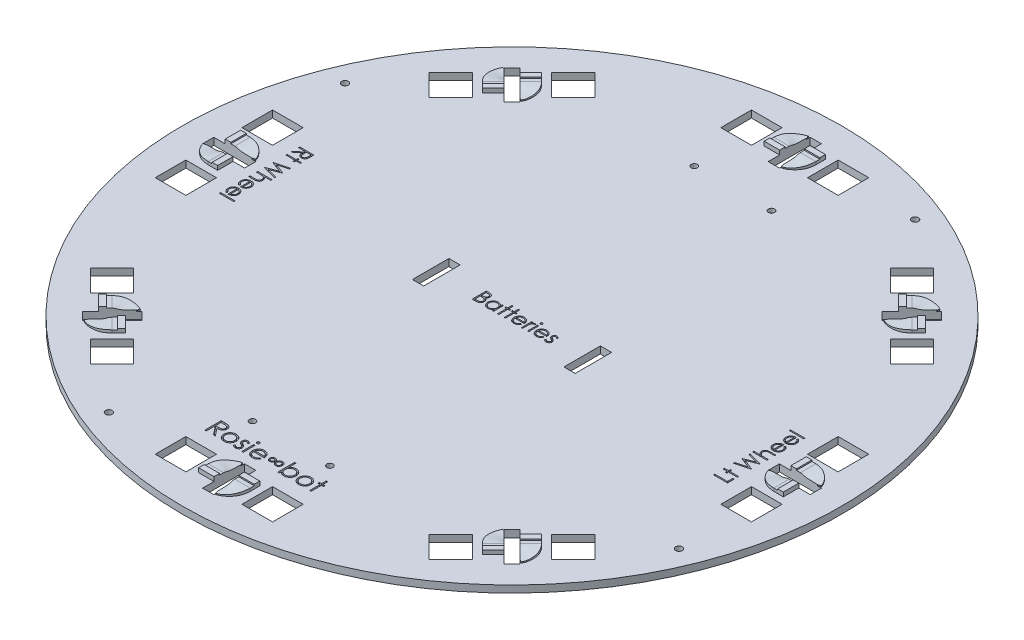
SolidWorks part; units mm, degrees
other "DetailItem1"
ref_plane "Front" through (0, 0, 0) normal (0, 0, 1) x (1, 0, 0)
ref_plane "Top" through (0, 0, 0) normal (0, 1, 0) x (1, 0, 0)
ref_plane "Right" through (0, 0, 0) normal (1, 0, 0) x (0, 0, -1)
sketch "Sketch1" plane through (0, 0, 0) normal (0, 1, 0) x (1, 0, 0)
  circle A0 centre (0, 0) radius 149.225
  dimension "D1" = 298.45
extrude "Base" add sketch "Sketch1" along normal blind 3.175 contours A0
sketch "Sketch2" plane through (0, 3.175, 0) normal (0, 1, 0) x (1, 0, 0)
  line L1 (-2.54, -137.5833) -> (2.54, -137.5833)
  line L2 (-2.54, -137.5833) -> (-2.54, -118.5333)
  line L3 (-2.54, -118.5333) -> (2.54, -118.5333)
  line L4 (2.54, -137.5833) -> (2.54, -118.5333)
  circle A0 centre (0, 0) radius 149.225 construction
  point P4 (0, -118.5333)
  dimension "D1" = 5.08
  dimension "D2" = 19.05
  dimension "D3" = 137.5833
extrude "Cut-Extrude1" cut sketch "Sketch2" against normal up to next and the other way through all contours L1 L4 L3 L2
sketch "Sketch4" plane through (0, 3.175, 0) normal (0, 1, 0) x (1, 0, 0)
  line L0 (0, -128.0583) -> (-2.9434, -118.9995) construction
  line L1 (-2.9434, -118.9995) -> (0, -128.0583) construction
  line L2 (0, -128.0583) -> (-5.5987, -120.3525) construction
  line L3 (0, -128.0583) -> (-7.7059, -122.4597) construction
  line L4 (0, -128.0583) -> (-9.0588, -125.115) construction
  line L5 (0, -128.0583) -> (-9.525, -128.0583) construction
  line L9 (2.54, -118.5333) -> (-2.54, -118.5333) construction
  line L10 (2.54, -118.5333) -> (2.54, -137.5833) construction
  line L11 (-2.54, -118.5333) -> (-2.54, -137.5833) construction
  line L12 (2.54, -137.5833) -> (-2.54, -137.5833) construction
  circle A0 centre (0, -128.0583) radius 9.525 construction
  point P16 (0, -118.5333)
  point P19 (2.54, -128.0583)
  dimension "D1" = 18
  dimension "D2" = 18
  dimension "D3" = 18
  dimension "D4" = 18
  dimension "D5" = 18
ref_plane "Plane1" through (-37.6354, 0, 12.2285) normal (0.9511, 0, -0.309) x (-0.309, 0, -0.9511)
ref_plane "Plane2" through (-60.8954, 0, 44.2431) normal (0.809, 0, -0.5878) x (-0.5878, 0, -0.809)
ref_plane "Plane3" through (-60.8954, 0, 83.8153) normal (0.5878, 0, -0.809) x (-0.809, 0, -0.5878)
ref_plane "Plane4" through (-37.6354, 0, 115.8299) normal (0.309, 0, -0.9511) x (-0.9511, 0, -0.309)
ref_plane "Plane5" through (0, 0, 128.0583) normal (0, 0, -1) x (-1, 0, 0)
sketch "Sketch5" plane through (-37.6354, 0, 12.2285) normal (0.9511, 0, -0.309) x (-0.309, 0, -0.9511)
  line L0 (-111.947, 3.175) -> (-130.0646, 3.175) construction
  line L1 (-113.5711, 3.175) -> (-112.2657, 3.175)
  line L2 (-113.5711, 3.175) -> (-113.5711, 3.683)
  line L3 (-113.5711, 3.683) -> (-112.2657, 3.683)
  line L4 (-112.2657, 3.175) -> (-112.2657, 3.683)
  dimension "D2" = 0.508
sketch "Sketch6" plane through (-60.8954, 0, 44.2431) normal (0.809, 0, -0.5878) x (-0.5878, 0, -0.809)
  line L0 (-94.4025, 3.175) -> (-109.8143, 3.175) construction
  line L1 (-99.2801, 3.175) -> (-94.0764, 3.175)
  line L2 (-99.2801, 3.175) -> (-99.2801, 3.775)
  line L3 (-99.2801, 3.775) -> (-94.0764, 3.775)
  line L4 (-94.0764, 3.175) -> (-94.0764, 3.775)
  dimension "D2" = 0.6
sketch "Sketch7" plane through (-60.8954, 0, 83.8153) normal (0.5878, 0, -0.809) x (-0.809, 0, -0.5878)
  line L0 (-67.6172, 3.175) -> (-78.8146, 3.175) construction
  line L1 (-72.1312, 3.175) -> (-65.7458, 3.175)
  line L2 (-72.1312, 3.175) -> (-72.1312, 4.075)
  line L3 (-72.1312, 4.075) -> (-65.7458, 4.075)
  line L4 (-65.7458, 3.175) -> (-65.7458, 4.075)
  dimension "D2" = 0.9
sketch "Sketch10" plane through (-37.6354, 0, 115.8299) normal (0.309, 0, -0.9511) x (-0.9511, 0, -0.309)
  line L0 (-39.5722, 3.175) -> (-30.5134, 3.175) construction
  line L1 (-36.9015, 3.175) -> (-30.0472, 3.175)
  line L2 (-36.9015, 3.175) -> (-36.9015, 4.375)
  line L3 (-36.9015, 4.375) -> (-30.0472, 4.375)
  line L4 (-30.0472, 3.175) -> (-30.0472, 4.375)
  dimension "D3" = 1.2
sketch "Sketch11" plane through (0, 0, 128.0583) normal (0, 0, -1) x (-1, 0, 0)
  line L0 (0, 3.175) -> (9.525, 3.175) construction
  line L1 (2.54, 3.175) -> (9.525, 3.175)
  line L2 (2.54, 3.175) -> (2.54, 4.475)
  line L3 (2.54, 4.475) -> (9.525, 4.475)
  line L4 (9.525, 3.175) -> (9.525, 4.475)
  dimension "D3" = 1.3
loft "Loft1" add profiles "Sketch5", "Sketch6", "Sketch7", "Sketch10", "Sketch11" connector at (-2.54, 3.683, 120.241) connector at (-2.54, 3.775, 124.5623) connector at (-2.54, 4.075, 126.2129) connector at (-2.54, 4.375, 127.233) connector at (-2.54, 4.475, 128.0583)
sketch "Sketch13" plane through (-104.9799, 0, 128.0583) normal (0, 0, -1) x (-1, 0, 0)
  line L6 (-95.4549, 3.175) -> (-102.4399, 3.175)
  line L7 (-95.4549, 3.175) -> (-95.4549, 4.475)
  line L8 (-95.4549, 4.475) -> (-102.4399, 4.475)
  line L9 (-102.4399, 3.175) -> (-102.4399, 4.475)
extrude "Boss-Extrude4" add sketch "Sketch13" against normal blind 1.7907
sketch "Sketch25" plane through (0, 0, 129.849) normal (0, 0, 1) x (1, 0, 0)
  line L0 (-9.525, 4.475) -> (-2.54, 4.475) construction
  line L1 (-9.525, 3.175) -> (-2.54, 3.175)
  line L2 (-9.525, 3.175) -> (-9.525, 5.075)
  line L3 (-9.525, 5.075) -> (-2.54, 5.075)
  line L4 (-2.54, 3.175) -> (-2.54, 5.075)
  dimension "D1" = 0.6
extrude "Boss-Extrude5" add sketch "Sketch25" along normal blind 2.54
sketch "Sketch14" plane through (-2.54, 0, 0) normal (1, 0, 0) x (0, 0, -1)
  line L0 (-128.0583, 3.175) -> (-128.0583, 0) construction
  line L1 (-118.5333, 0) -> (-137.5833, 0) construction
ref_plane "Plane6" through (0, 0, 0) normal (1, 0, 0) x (0, 0, -1)
sketch "Sketch15" plane through (0, 0, 0) normal (1, 0, 0) x (0, 0, -1)
  line L0 (-128.0583, 0) -> (-128.0583, 3.175) construction
pattern_circular "CirPattern1" count 2 over 360 about axis through (0, 0, 128.0583) along (0, 1, 0) of "Loft1", "Boss-Extrude5", "Boss-Extrude4" reverse direction yes
ref_axis "Axis1" through (0, 50, 0) along (0, -1, 0)
pattern_circular "CirPattern5" count 8 over 360 about axis through (0, 50, 0) along (0, -1, 0) of "CirPattern1", "Cut-Extrude1"
sketch "Sketch18" plane through (0, 3.175, 0) normal (0, 1, 0) x (1, 0, 0)
  line L4 (0, -149.225) -> (0, 149.225) construction
  line L5 (0, -1.7463) -> (0, 1.7463) construction
  line L6 (-149.225, 0) -> (149.225, 0) construction
  circle A8 centre (0, 0) radius 149.225 construction
sketch "Sketch19" plane through (0, 3.175, 0) normal (0, 1, 0) x (1, 0, 0)
  line L0 (-53.4609, -129.066) -> (0, 0) construction
  line L1 (0, -149.225) -> (0, 149.225) construction
  circle A1 centre (-53.4609, -129.066) radius 1.5
  dimension "D1" = 139.7
  dimension "D4" = 3
  dimension "D5" = 22.5
extrude "Cut-Extrude2" cut sketch "Sketch19" against normal through all
pattern_circular "CirPattern7" count 4 over 360 about axis through (0, 50, 0) along (0, -1, 0) of "Cut-Extrude2"
sketch "Sketch23" plane through (0, 3.175, 0) normal (0, 1, 0) x (1, 0, 0)
  line L9 (-2.54, -132.389) -> (-2.54, -137.5833) construction
  line L10 (-26.5557, -121.1305) -> (-12.7, -121.1305)
  line L11 (-26.5557, -121.1305) -> (-26.5557, -134.9862)
  line L16 (-26.5557, -134.9862) -> (-12.7, -134.9862)
  line L17 (-12.7, -121.1305) -> (-12.7, -134.9862)
  line L19 (2.54, -118.5333) -> (2.54, -123.7276) construction
  line L20 (0, -50) -> (0, 50) construction
  line L21 (12.7, -121.1305) -> (12.7, -134.9862)
  line L22 (26.5557, -134.9862) -> (12.7, -134.9862)
  line L23 (26.5557, -121.1305) -> (26.5557, -134.9862)
  line L24 (26.5557, -121.1305) -> (12.7, -121.1305)
  point P8 (-2.54, -134.9862)
  point P9 (2.54, -121.1305)
  dimension "D2" = 10.16
extrude "Cut-Extrude6" cut sketch "Sketch23" against normal through all
pattern_circular "CirPattern8" count 8 over 360 about axis through (0, 50, 0) along (0, -1, 0) of "Cut-Extrude6"
sketch "Sketch16" plane through (0, 3.175, 0) normal (0, 1, 0) x (1, 0, 0)
  line L1 (-16.4163, -2.4279) -> (16.4163, -2.4279) construction
  line L2 (0, -149.225) -> (0, 149.225) construction
  line L3 (-114.3, 19.05) -> (-114.3, -19.05) construction
  line L4 (-149.225, 0) -> (149.225, 0) construction
  line L5 (114.3, 19.05) -> (114.3, -19.05) construction
  line L6 (-25.719, -114.3) -> (25.719, -114.3) construction
  circle A2 centre (0, 0) radius 114.3 construction
  text T0 "Rosie∞bot\r\n" font "Century Gothic" height in points 28
  text T1 "Batteries"
  text T2 "Rt Wheel\r\n"
  text T3 "Lt Wheel"
  point P4 (-114.3, 0)
  point P7 (0, -114.3)
  point P10 (0, -2.4279)
  point P15 (114.3, 0)
  dimension "D7" = 228.6
  dimension "D1" = 32.8326
  dimension "D2" = 38.1
  dimension "D3" = 51.438
extrude "Cut-Extrude4" cut sketch "Sketch16" against normal blind 1.27
sketch "Sketch28" plane through (0, 0, 0) normal (0, -1, 0) x (-1, 0, 0)
  line L0 (19.05, 101.6) -> (-19.05, 101.6) construction
  line L1 (0, -149.225) -> (0, 149.225) construction
  line L2 (149.225, 0) -> (-149.225, 0) construction
  line L3 (19.05, -101.6) -> (-19.05, -101.6) construction
  text T0 "Bk Caster"
  text T1 "Ft Caster"
  point P2 (0, 101.6)
  point P6 (0, -101.6)
  dimension "D1" = 101.6
  dimension "D2" = 38.1
  dimension "D3" = 101.6
extrude "Cut-Extrude9" cut sketch "Sketch28" against normal blind 1.27
sketch "Sketch26" plane through (0, 3.175, 0) normal (0, 1, 0) x (1, 0, 0)
  line L0 (-149.225, 0) -> (149.225, 0) construction
  line L1 (-36.83, 8.255) -> (-31.75, 8.255)
  line L2 (-36.83, 8.255) -> (-36.83, -8.255)
  line L3 (-36.83, -8.255) -> (-31.75, -8.255)
  line L4 (-31.75, 8.255) -> (-31.75, -8.255)
  line L5 (0, -149.225) -> (0, 149.225) construction
  point P4 (-36.83, 0)
  dimension "D1" = 16.51
  dimension "D2" = 5.08
  dimension "D3" = 31.75
extrude "Cut-Extrude7" cut sketch "Sketch26" against normal through all
mirror "Mirror1" about plane through (0, 0, 0) normal (1, 0, 0) of "Cut-Extrude7"
sketch "Sketch27" plane through (0, 0, 0) normal (0, -1, 0) x (1, 0, 0)
  line L0 (0, 149.225) -> (0, -149.225) construction
  line L1 (-149.225, 0) -> (149.225, 0) construction
  circle A0 centre (-17.5, -100) radius 1.4
  dimension "D3" = 2.8
  dimension "D1" = 17.5
  dimension "D2" = 100
extrude "Cut-Extrude8" cut sketch "Sketch27" against normal through all both and the other way through all
mirror "Mirror2" about plane through (0, 0, 0) normal (1, 0, 0) of "Cut-Extrude8"
mirror "Mirror3" about plane through (0, 0, 0) normal (0, 0, 1) of "Mirror2"
